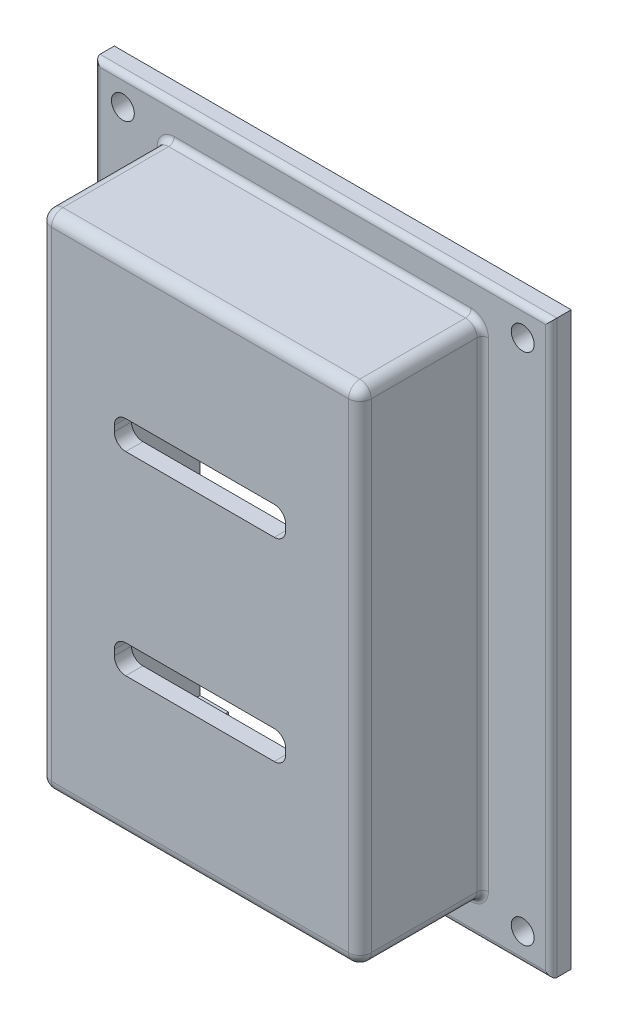
SolidWorks part; units mm, degrees
material "ABS"
ref_plane "Front Plane" through (0, 0, 0) normal (0, 0, 1) x (1, 0, 0)
ref_plane "Top Plane" through (0, 0, 0) normal (0, 1, 0) x (1, 0, 0)
ref_plane "Right Plane" through (0, 0, 0) normal (1, 0, 0) x (0, 0, -1)
sketch "Sketch1" plane through (0, 0, 0) normal (0, 0, 1) x (1, 0, 0)
  line L1 (-40, 50) -> (40, 50)
  line L2 (-40, 50) -> (-40, -50)
  line L3 (-40, -50) -> (40, -50)
  line L4 (40, 50) -> (40, -50)
  line L5 (-40, 50) -> (40, -50) construction
  line L6 (-40, -50) -> (40, 50) construction
  point P0 (0, 0)
  dimension "D1" = 100
  dimension "D2" = 80
extrude "Boss-Extrude1" add sketch "Sketch1" along normal blind 3.5
sketch "Sketch3" plane through (0, 0, 3.5) normal (0, 0, 1) x (1, 0, 0)
  line L1 (-28, 44) -> (28, 44)
  line L2 (-28, 44) -> (-28, -44)
  line L3 (-28, -44) -> (28, -44)
  line L4 (28, 44) -> (28, -44)
  line L5 (-28, 44) -> (28, -44) construction
  line L6 (-28, -44) -> (28, 44) construction
  point P0 (0, 0)
  dimension "D1" = 56
  dimension "D2" = 88
extrude "Boss-Extrude2" add sketch "Sketch3" along normal blind 21.5
sketch "Sketch4" plane through (0, 0, 0) normal (0, 0, -1) x (-1, 0, 0)
  line L1 (-25, 41) -> (25, 41)
  line L2 (-25, 41) -> (-25, -41)
  line L3 (-25, -41) -> (25, -41)
  line L4 (25, 41) -> (25, -41)
  line L5 (-25, 41) -> (25, -41) construction
  line L6 (-25, -41) -> (25, 41) construction
  point P0 (0, 0)
  dimension "D1" = 50
  dimension "D2" = 82
extrude "Cut-Extrude4" cut sketch "Sketch4" against normal blind 16
sketch "Sketch7" plane through (0, 0, 16) normal (0, 0, -1) x (-1, 0, 0)
  line L0 (-18, 41) -> (18, 41)
  line L1 (25, 41) -> (-25, 41) construction
  line L2 (25, 41) -> (-25, 41) construction
  line L3 (18, 41) -> (18, 34)
  line L4 (18, 34) -> (25, 34)
  line L5 (25, -41) -> (25, 41) construction
  line L6 (25, 34) -> (25, -34)
  line L7 (25, -34) -> (18, -34)
  line L8 (18, -34) -> (18, -41)
  line L9 (-25, -41) -> (25, -41) construction
  line L10 (18, -41) -> (-18, -41)
  line L11 (-18, -41) -> (-18, -34)
  line L12 (-18, -34) -> (-25, -34)
  line L13 (-25, 41) -> (-25, -41) construction
  line L14 (-25, -34) -> (-25, 34)
  line L15 (-25, 34) -> (-18, 34)
  line L16 (-18, 34) -> (-18, 41)
  dimension "D1" = 68
  dimension "D2" = 7
  dimension "D3" = 36
  dimension "D4" = 7
  dimension "D5" = 68
  dimension "D6" = 36
  dimension "D7" = 7
  dimension "D8" = 7
extrude "Cut-Extrude5" cut sketch "Sketch7" against normal blind 6
sketch "Sketch8" plane through (0, 0, 25) normal (0, 0, 1) x (1, 0, 0)
  line L1 (-15, -19.5) -> (15, -19.5)
  line L2 (-15, -19.5) -> (-15, -14.5)
  line L3 (-15, -14.5) -> (15, -14.5)
  line L4 (15, -19.5) -> (15, -14.5)
  line L5 (-15, -19.5) -> (15, -14.5) construction
  line L6 (-15, -14.5) -> (15, -19.5) construction
  point P0 (0, -17)
  dimension "D1" = 5
  dimension "D2" = 17
  dimension "D3" = 30
extrude "Cut-Extrude6" cut sketch "Sketch8" against normal blind 6
mirror "Mirror1" about plane through (0, 0, 0) normal (0, 1, 0) of "Cut-Extrude6"
sketch "Sketch9" plane through (0, -50, 0) normal (0, -1, 0) x (1, 0, 0)
  line L0 (-40, 0) -> (40, 0) construction
  line L1 (-20, 0) -> (20, 0)
  line L2 (-20, 0) -> (-20, 12)
  line L3 (-20, 12) -> (20, 12)
  line L4 (20, 0) -> (20, 12)
  line L5 (-40, 3.5) -> (-40, 0) construction
  dimension "D1" = 20
  dimension "D2" = 40
  dimension "D3" = 12
extrude "Cut-Extrude7" cut sketch "Sketch9" against normal up to next
sketch "Sketch10" plane through (0, 0, 0) normal (0, 0, -1) x (-1, 0, 0)
  line L1 (-35, 45) -> (35, 45)
  line L2 (-35, 45) -> (-35, -45)
  line L3 (-35, -45) -> (35, -45)
  line L4 (35, 45) -> (35, -45)
  line L5 (-35, 45) -> (35, -45) construction
  line L6 (-35, -45) -> (35, 45) construction
  point P0 (0, 0)
  dimension "D1" = 90
  dimension "D2" = 70
hole_wizard "Ø4.0mm Dowel Hole1" positions "Sketch11" profile "Sketch12" hole size "Ø4.0" standard "ANSI Metric" end condition through all
sketch "Sketch11" plane through (0, 0, 0) normal (0, 0, -1) x (-1, 0, 0)
  point P0 (-35, 45)
  point P3 (35, 45)
  point P6 (35, -45)
  point P9 (-35, -45)
sketch "Sketch12" plane through (35, 45, 0) normal (1, 0, 0) x (0, 1, 0)
  line L0 (0, 0) -> (0, 25)
  line L1 (0, 25) -> (2, 25)
  line L2 (2, 25) -> (2, 0)
  line L5 (2, 0) -> (0, 0)
  line L11 (0, -6.35) -> (0, 107.95) construction
  dimension "Thru Hole Dia." = 4
  dimension "Thru Hole Depth" = 25
fillet "Fillet1" radius 7 4 edges at (-18, 34, 19) (18, 34, 19) (18, -34, 19) (-18, -34, 19)
fillet "Fillet2" radius 2 15 edges at (28, -44, 14.25) (-28, -44, 14.25) (-15, 19.5, 23.5) (15, 19.5, 23.5) (15, 14.5, 23.5) (-15, 14.5, 23.5) (-15, -19.5, 23.5) (-15, -14.5, 23.5) (15, -14.5, 23.5) (15, -19.5, 23.5) (-28, 0, 25) (-28, 44, 14.25) (0, 44, 25) (28, 0, 25) (28, 44, 14.25)
fillet "Fillet3" radius 1 14 edges at (23, -44, 3.5) (27.4142, -43.4142, 3.5) (28, 0, 3.5) (27.4142, 43.4142, 3.5) (0, 44, 3.5) (-27.4142, 43.4142, 3.5) (-23, -44, 3.5) (-27.4142, -43.4142, 3.5) (30, -50, 3.5) (40, 0, 3.5) (0, 50, 3.5) (-30, -50, 3.5) (-40, 0, 3.5) (-28, 0, 3.5)
fillet "Fillet4" radius 2 3 edges at (-27.4142, -43.4142, 24.4142) (27.4142, -43.4142, 24.4142) (0, -44, 25)
